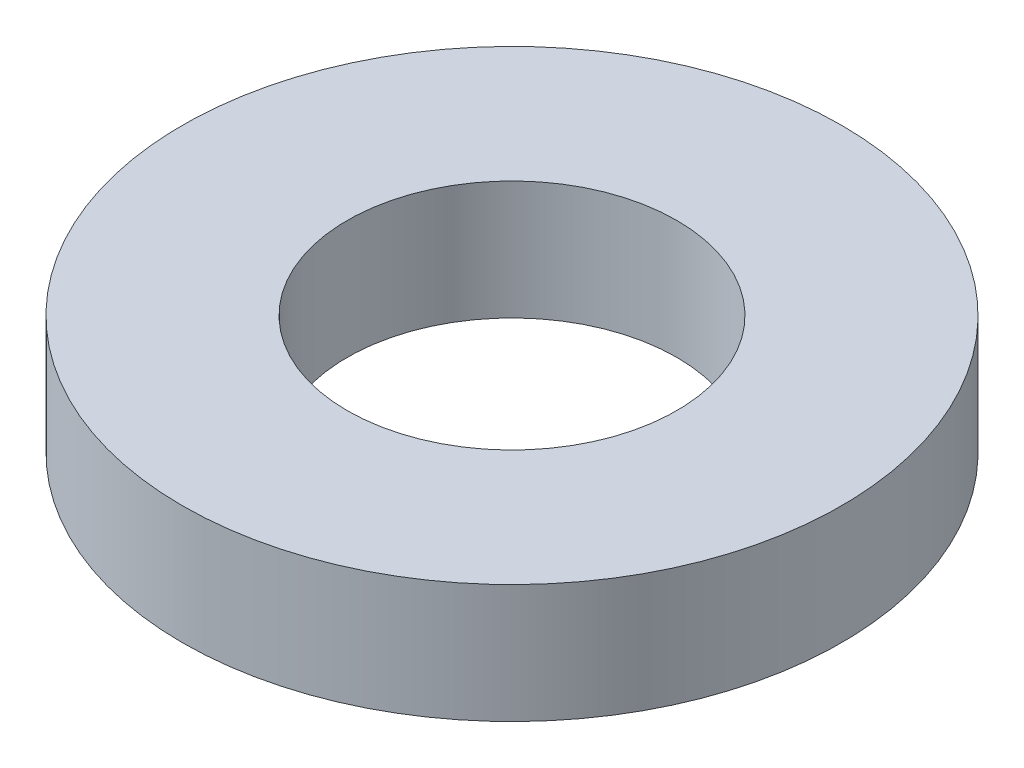
SolidWorks part; units mm, degrees
ref_plane "Front Plane" through (0, 0, 0) normal (0, 0, 1) x (1, 0, 0)
ref_plane "Top Plane" through (0, 0, 0) normal (0, 1, 0) x (1, 0, 0)
ref_plane "Right Plane" through (0, 0, 0) normal (1, 0, 0) x (0, 0, -1)
sketch "Sketch1" plane through (0, 0, 0) normal (0, 1, 0) x (1, 0, 0)
  circle A0 centre (0, 0) radius 75
  dimension "FLANGE_OD" = 150
extrude "Boss-Extrude1" add sketch "Sketch1" along normal blind 27
sketch "Sketch2" plane through (0, 0, 0) normal (0, 1, 0) x (1, 0, 0)
  circle A0 centre (0, 0) radius 37.5
  dimension "BORE_D" = 75
extrude "Cut-Extrude1" cut sketch "Sketch2" along normal through all
sketch "Sketch3" plane through (0, 27, 0) normal (0, 1, 0) x (1, 0, 0)
  circle A0 centre (0, 0) radius 24.1289 construction
  circle A1 centre (-24.1289, 0) radius 5.3268
  dimension "BOLT_D" = 10.6536
  dimension "BOLT_PCD" = 48.2578
extrude "Cut-Extrude2" cut sketch "Sketch3" against normal blind 25.5474 rebuild error yes
pattern_circular "CirPattern1" count 8 over 360 rebuild error yes
